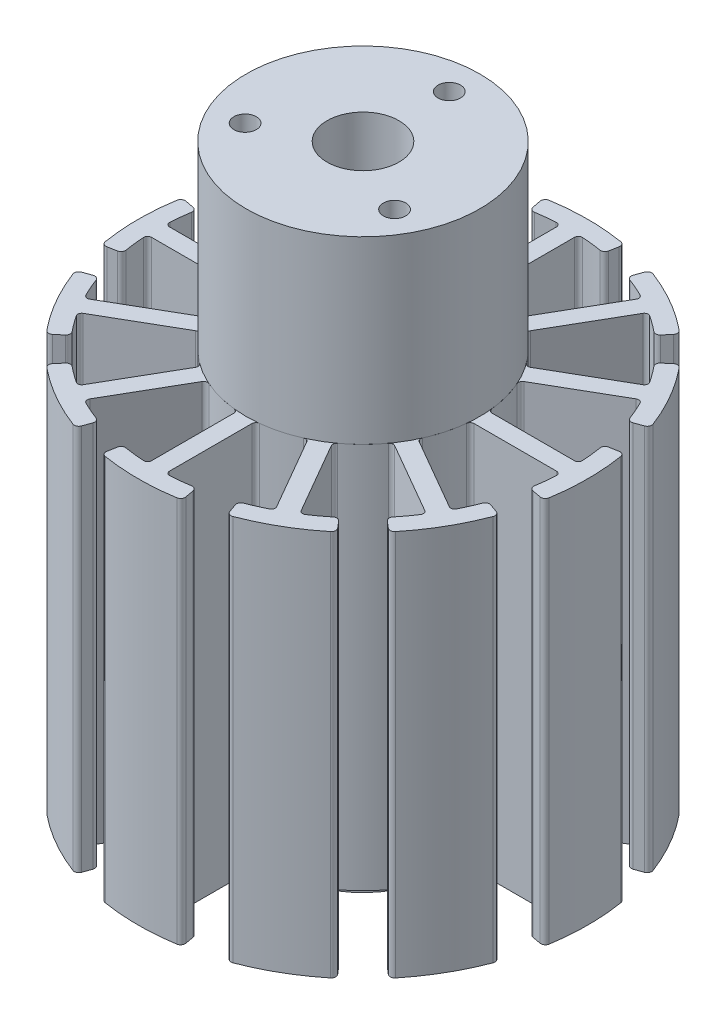
SolidWorks part; units mm, degrees
ref_plane "Front Plane" through (0, 0, 0) normal (0, 0, 1) x (1, 0, 0)
ref_plane "Top Plane" through (0, 0, 0) normal (0, 1, 0) x (1, 0, 0)
ref_plane "Right Plane" through (0, 0, 0) normal (1, 0, 0) x (0, 0, -1)
sketch "Sketch1" plane through (0, 0, 0) normal (0, 1, 0) x (1, 0, 0)
  circle A0 centre (0, 0) radius 13
  dimension "D1" = 26
extrude "Boss-Extrude1" add sketch "Sketch1" along normal blind 20
sketch "Sketch2" plane through (0, 20, 0) normal (0, 1, 0) x (1, 0, 0)
  line L0 (0, 0) -> (0, 11.9477) construction
  circle A0 centre (0, 9.6) radius 1.25
  circle A1 centre (8.3138, -4.8) radius 1.25
  circle A2 centre (-8.3138, -4.8) radius 1.25
  point P12 (0, 0)
  dimension "D1" = 9.6
  dimension "D2" = 3
extrude "Cut-Extrude1" cut sketch "Sketch2" against normal blind 5
sketch "Sketch4" plane through (0, 0, 0) normal (0, -1, 0) x (1, 0, 0)
  line L6 (0, 13) -> (0, 25) construction
  line L12 (1, 13.3636) -> (1, 22.5128)
  line L13 (-1, 13.3636) -> (-1, 22.5128)
  line L15 (4.3912, 24.0981) -> (4.2119, 23.1141)
  line L17 (-4.3912, 24.0981) -> (-4.2119, 23.1141)
  line L18 (4.1232, 22.6274) -> (4.4817, 24.595) construction
  line L19 (-4.1232, 22.6274) -> (-4.4817, 24.595) construction
  line L20 (15.8519, 18.674) -> (15.2046, 17.9114)
  line L21 (8.2462, 23.0651) -> (7.9094, 22.1233)
  line L22 (14.8845, 17.5343) -> (16.1788, 19.059) construction
  line L23 (7.7429, 21.6575) -> (8.4162, 23.5408) construction
  line L24 (7.5478, 11.0732) -> (12.1224, 18.9967)
  line L25 (5.8158, 12.0732) -> (10.3904, 19.9967)
  line L26 (23.0651, 8.2462) -> (22.1233, 7.9094)
  line L27 (18.674, 15.8519) -> (17.9114, 15.2046)
  line L28 (21.6575, 7.7429) -> (23.5408, 8.4162) construction
  line L29 (17.5343, 14.8845) -> (19.059, 16.1788) construction
  line L30 (12.0732, 5.8158) -> (19.9967, 10.3904)
  line L31 (11.0732, 7.5478) -> (18.9967, 12.1224)
  line L32 (24.0981, -4.3912) -> (23.1141, -4.2119)
  line L33 (24.0981, 4.3912) -> (23.1141, 4.2119)
  line L34 (22.6274, -4.1232) -> (24.595, -4.4817) construction
  line L35 (22.6274, 4.1232) -> (24.595, 4.4817) construction
  line L36 (13.3636, -1) -> (22.5128, -1)
  line L37 (13.3636, 1) -> (22.5128, 1)
  line L38 (18.674, -15.8519) -> (17.9114, -15.2046)
  line L39 (23.0651, -8.2462) -> (22.1233, -7.9094)
  line L40 (17.5343, -14.8845) -> (19.059, -16.1788) construction
  line L41 (21.6575, -7.7429) -> (23.5408, -8.4162) construction
  line L42 (11.0732, -7.5478) -> (18.9967, -12.1224)
  line L43 (12.0732, -5.8158) -> (19.9967, -10.3904)
  line L44 (8.2462, -23.0651) -> (7.9094, -22.1233)
  line L45 (15.8519, -18.674) -> (15.2046, -17.9114)
  line L46 (7.7429, -21.6575) -> (8.4162, -23.5408) construction
  line L47 (14.8845, -17.5343) -> (16.1788, -19.059) construction
  line L48 (5.8158, -12.0732) -> (10.3904, -19.9967)
  line L49 (7.5478, -11.0732) -> (12.1224, -18.9967)
  line L50 (-4.3912, -24.0981) -> (-4.2119, -23.1141)
  line L51 (4.3912, -24.0981) -> (4.2119, -23.1141)
  line L52 (-4.1232, -22.6274) -> (-4.4817, -24.595) construction
  line L53 (4.1232, -22.6274) -> (4.4817, -24.595) construction
  line L54 (-1, -13.3636) -> (-1, -22.5128)
  line L55 (1, -13.3636) -> (1, -22.5128)
  line L56 (-15.8519, -18.674) -> (-15.2046, -17.9114)
  line L57 (-8.2462, -23.0651) -> (-7.9094, -22.1233)
  line L58 (-14.8845, -17.5343) -> (-16.1788, -19.059) construction
  line L59 (-7.7429, -21.6575) -> (-8.4162, -23.5408) construction
  line L60 (-7.5478, -11.0732) -> (-12.1224, -18.9967)
  line L61 (-5.8158, -12.0732) -> (-10.3904, -19.9967)
  line L62 (-23.0651, -8.2462) -> (-22.1233, -7.9094)
  line L63 (-18.674, -15.8519) -> (-17.9114, -15.2046)
  line L64 (-21.6575, -7.7429) -> (-23.5408, -8.4162) construction
  line L65 (-17.5343, -14.8845) -> (-19.059, -16.1788) construction
  line L66 (-12.0732, -5.8158) -> (-19.9967, -10.3904)
  line L67 (-11.0732, -7.5478) -> (-18.9967, -12.1224)
  line L68 (-24.0981, 4.3912) -> (-23.1141, 4.2119)
  line L69 (-24.0981, -4.3912) -> (-23.1141, -4.2119)
  line L70 (-22.6274, 4.1232) -> (-24.595, 4.4817) construction
  line L71 (-22.6274, -4.1232) -> (-24.595, -4.4817) construction
  line L72 (-13.3636, 1) -> (-22.5128, 1)
  line L73 (-13.3636, -1) -> (-22.5128, -1)
  line L74 (-18.674, 15.8519) -> (-17.9114, 15.2046)
  line L75 (-23.0651, 8.2462) -> (-22.1233, 7.9094)
  line L76 (-17.5343, 14.8845) -> (-19.059, 16.1788) construction
  line L77 (-21.6575, 7.7429) -> (-23.5408, 8.4162) construction
  line L78 (-11.0732, 7.5478) -> (-18.9967, 12.1224)
  line L79 (-12.0732, 5.8158) -> (-19.9967, 10.3904)
  line L80 (-8.2462, 23.0651) -> (-7.9094, 22.1233)
  line L81 (-15.8519, 18.674) -> (-15.2046, 17.9114)
  line L82 (-7.7429, 21.6575) -> (-8.4162, 23.5408) construction
  line L83 (-14.8845, 17.5343) -> (-16.1788, 19.059) construction
  line L84 (-5.8158, 12.0732) -> (-10.3904, 19.9967)
  line L85 (-7.5478, 11.0732) -> (-12.1224, 18.9967)
  arc A0 (3.9789, 24.6813) -> (-3.9789, 24.6813) centre (0, 0) ccw
  arc A1 (3.6408, 22.71) -> (1.4693, 22.953) centre (0, 0) ccw
  arc A2 (-1.3938, 12.9251) -> (-5.2555, 11.8903) centre (0, 0) ccw
  circle A3 centre (0, 0) radius 13 construction
  arc A4 (-12.7489, 19.1433) -> (-14.8845, 17.5343) centre (0, 0) ccw
  arc A5 (-12.5, 21.6506) -> (-16.1788, 19.059) centre (0, 0) ccw
  arc A6 (-4.3912, 24.0981) -> (-3.9789, 24.6813) centre (-3.8993, 24.1877) cw
  arc A7 (-4.2119, 23.1141) -> (-3.6408, 22.71) centre (-3.72, 23.2037) ccw
  arc A8 (4.2119, 23.1141) -> (3.6408, 22.71) centre (3.72, 23.2037) cw
  arc A9 (3.9789, 24.6813) -> (4.3912, 24.0981) centre (3.8993, 24.1877) cw
  arc A10 (-1.4693, 22.953) -> (-3.6408, 22.71) centre (0, 0) ccw
  arc A11 (-1, 22.5128) -> (-1.4693, 22.953) centre (-1.4411, 22.5128) ccw
  arc A12 (1, 22.5128) -> (1.4693, 22.953) centre (1.4411, 22.5128) cw
  arc A13 (-1, 13.3636) -> (-1.3938, 12.9251) centre (-1.4411, 13.3636) cw
  arc A14 (1, 13.3636) -> (1.3938, 12.9251) centre (1.4411, 13.3636) ccw
  arc A15 (5.2555, 11.8903) -> (-5.2555, 11.8903) centre (0, 0) ccw
  arc A16 (15.7865, 19.3852) -> (8.8949, 23.3641) centre (0, 0) ccw
  arc A17 (14.5081, 17.847) -> (12.7489, 19.1433) centre (0, 0) ccw
  arc A18 (8.2462, 23.0651) -> (8.8949, 23.3641) centre (8.717, 22.8968) cw
  arc A19 (7.9094, 22.1233) -> (8.202, 21.4879) centre (8.3803, 21.955) ccw
  arc A20 (15.2046, 17.9114) -> (14.5081, 17.847) centre (14.8234, 18.235) cw
  arc A21 (15.7865, 19.3852) -> (15.8519, 18.674) centre (15.4707, 18.9975) cw
  arc A22 (10.2041, 20.6125) -> (8.202, 21.4879) centre (0, 0) ccw
  arc A23 (10.3904, 19.9967) -> (10.2041, 20.6125) centre (10.0084, 20.2172) ccw
  arc A24 (12.1224, 18.9967) -> (12.7489, 19.1433) centre (12.5044, 18.7761) cw
  arc A25 (5.8158, 12.0732) -> (5.2555, 11.8903) centre (5.4338, 12.2938) cw
  arc A26 (23.3641, 8.8949) -> (19.3852, 15.7865) centre (0, 0) ccw
  arc A27 (21.4879, 8.202) -> (20.6125, 10.2041) centre (0, 0) ccw
  arc A28 (18.674, 15.8519) -> (19.3852, 15.7865) centre (18.9975, 15.4707) cw
  arc A29 (17.9114, 15.2046) -> (17.847, 14.5081) centre (18.235, 14.8234) ccw
  arc A30 (22.1233, 7.9094) -> (21.4879, 8.202) centre (21.955, 8.3803) cw
  arc A31 (23.3641, 8.8949) -> (23.0651, 8.2462) centre (22.8968, 8.717) cw
  arc A32 (19.1433, 12.7489) -> (17.847, 14.5081) centre (0, 0) ccw
  arc A33 (18.9967, 12.1224) -> (19.1433, 12.7489) centre (18.7761, 12.5044) ccw
  arc A34 (19.9967, 10.3904) -> (20.6125, 10.2041) centre (20.2172, 10.0084) cw
  arc A35 (11.0732, 7.5478) -> (10.4965, 7.6696) centre (10.8527, 7.9298) cw
  arc A36 (24.6813, -3.9789) -> (24.6813, 3.9789) centre (0, 0) ccw
  arc A37 (22.71, -3.6408) -> (22.953, -1.4693) centre (0, 0) ccw
  arc A38 (24.0981, 4.3912) -> (24.6813, 3.9789) centre (24.1877, 3.8993) cw
  arc A39 (23.1141, 4.2119) -> (22.71, 3.6408) centre (23.2037, 3.72) ccw
  arc A40 (23.1141, -4.2119) -> (22.71, -3.6408) centre (23.2037, -3.72) cw
  arc A41 (24.6813, -3.9789) -> (24.0981, -4.3912) centre (24.1877, -3.8993) cw
  arc A42 (22.953, 1.4693) -> (22.71, 3.6408) centre (0, 0) ccw
  arc A43 (22.5128, 1) -> (22.953, 1.4693) centre (22.5128, 1.4411) ccw
  arc A44 (22.5128, -1) -> (22.953, -1.4693) centre (22.5128, -1.4411) cw
  arc A45 (13.3636, 1) -> (12.9251, 1.3938) centre (13.3636, 1.4411) cw
  arc A46 (19.3852, -15.7865) -> (23.3641, -8.8949) centre (0, 0) ccw
  arc A47 (17.847, -14.5081) -> (19.1433, -12.7489) centre (0, 0) ccw
  arc A48 (23.0651, -8.2462) -> (23.3641, -8.8949) centre (22.8968, -8.717) cw
  arc A49 (22.1233, -7.9094) -> (21.4879, -8.202) centre (21.955, -8.3803) ccw
  arc A50 (17.9114, -15.2046) -> (17.847, -14.5081) centre (18.235, -14.8234) cw
  arc A51 (19.3852, -15.7865) -> (18.674, -15.8519) centre (18.9975, -15.4707) cw
  arc A52 (20.6125, -10.2041) -> (21.4879, -8.202) centre (0, 0) ccw
  arc A53 (19.9967, -10.3904) -> (20.6125, -10.2041) centre (20.2172, -10.0084) ccw
  arc A54 (18.9967, -12.1224) -> (19.1433, -12.7489) centre (18.7761, -12.5044) cw
  arc A55 (12.0732, -5.8158) -> (11.8903, -5.2555) centre (12.2938, -5.4338) cw
  arc A56 (8.8949, -23.3641) -> (15.7865, -19.3852) centre (0, 0) ccw
  arc A57 (8.202, -21.4879) -> (10.2041, -20.6125) centre (0, 0) ccw
  arc A58 (15.8519, -18.674) -> (15.7865, -19.3852) centre (15.4707, -18.9975) cw
  arc A59 (15.2046, -17.9114) -> (14.5081, -17.847) centre (14.8234, -18.235) ccw
  arc A60 (7.9094, -22.1233) -> (8.202, -21.4879) centre (8.3803, -21.955) cw
  arc A61 (8.8949, -23.3641) -> (8.2462, -23.0651) centre (8.717, -22.8968) cw
  arc A62 (12.7489, -19.1433) -> (14.5081, -17.847) centre (0, 0) ccw
  arc A63 (12.1224, -18.9967) -> (12.7489, -19.1433) centre (12.5044, -18.7761) ccw
  arc A64 (10.3904, -19.9967) -> (10.2041, -20.6125) centre (10.0084, -20.2172) cw
  arc A65 (7.5478, -11.0732) -> (7.6696, -10.4965) centre (7.9298, -10.8527) cw
  arc A66 (-3.9789, -24.6813) -> (3.9789, -24.6813) centre (0, 0) ccw
  arc A67 (-3.6408, -22.71) -> (-1.4693, -22.953) centre (0, 0) ccw
  arc A68 (4.3912, -24.0981) -> (3.9789, -24.6813) centre (3.8993, -24.1877) cw
  arc A69 (4.2119, -23.1141) -> (3.6408, -22.71) centre (3.72, -23.2037) ccw
  arc A70 (-4.2119, -23.1141) -> (-3.6408, -22.71) centre (-3.72, -23.2037) cw
  arc A71 (-3.9789, -24.6813) -> (-4.3912, -24.0981) centre (-3.8993, -24.1877) cw
  arc A72 (1.4693, -22.953) -> (3.6408, -22.71) centre (0, 0) ccw
  arc A73 (1, -22.5128) -> (1.4693, -22.953) centre (1.4411, -22.5128) ccw
  arc A74 (-1, -22.5128) -> (-1.4693, -22.953) centre (-1.4411, -22.5128) cw
  arc A75 (1, -13.3636) -> (1.3938, -12.9251) centre (1.4411, -13.3636) cw
  arc A76 (-15.7865, -19.3852) -> (-8.8949, -23.3641) centre (0, 0) ccw
  arc A77 (-14.5081, -17.847) -> (-12.7489, -19.1433) centre (0, 0) ccw
  arc A78 (-8.2462, -23.0651) -> (-8.8949, -23.3641) centre (-8.717, -22.8968) cw
  arc A79 (-7.9094, -22.1233) -> (-8.202, -21.4879) centre (-8.3803, -21.955) ccw
  arc A80 (-15.2046, -17.9114) -> (-14.5081, -17.847) centre (-14.8234, -18.235) cw
  arc A81 (-15.7865, -19.3852) -> (-15.8519, -18.674) centre (-15.4707, -18.9975) cw
  arc A82 (-10.2041, -20.6125) -> (-8.202, -21.4879) centre (0, 0) ccw
  arc A83 (-10.3904, -19.9967) -> (-10.2041, -20.6125) centre (-10.0084, -20.2172) ccw
  arc A84 (-12.1224, -18.9967) -> (-12.7489, -19.1433) centre (-12.5044, -18.7761) cw
  arc A85 (-5.8158, -12.0732) -> (-5.2555, -11.8903) centre (-5.4338, -12.2938) cw
  arc A86 (-23.3641, -8.8949) -> (-19.3852, -15.7865) centre (0, 0) ccw
  arc A87 (-21.4879, -8.202) -> (-20.6125, -10.2041) centre (0, 0) ccw
  arc A88 (-18.674, -15.8519) -> (-19.3852, -15.7865) centre (-18.9975, -15.4707) cw
  arc A89 (-17.9114, -15.2046) -> (-17.847, -14.5081) centre (-18.235, -14.8234) ccw
  arc A90 (-22.1233, -7.9094) -> (-21.4879, -8.202) centre (-21.955, -8.3803) cw
  arc A91 (-23.3641, -8.8949) -> (-23.0651, -8.2462) centre (-22.8968, -8.717) cw
  arc A92 (-19.1433, -12.7489) -> (-17.847, -14.5081) centre (0, 0) ccw
  arc A93 (-18.9967, -12.1224) -> (-19.1433, -12.7489) centre (-18.7761, -12.5044) ccw
  arc A94 (-19.9967, -10.3904) -> (-20.6125, -10.2041) centre (-20.2172, -10.0084) cw
  arc A95 (-11.0732, -7.5478) -> (-10.4965, -7.6696) centre (-10.8527, -7.9298) cw
  arc A96 (-24.6813, 3.9789) -> (-24.6813, -3.9789) centre (0, 0) ccw
  arc A97 (-22.71, 3.6408) -> (-22.953, 1.4693) centre (0, 0) ccw
  arc A98 (-24.0981, -4.3912) -> (-24.6813, -3.9789) centre (-24.1877, -3.8993) cw
  arc A99 (-23.1141, -4.2119) -> (-22.71, -3.6408) centre (-23.2037, -3.72) ccw
  arc A100 (-23.1141, 4.2119) -> (-22.71, 3.6408) centre (-23.2037, 3.72) cw
  arc A101 (-24.6813, 3.9789) -> (-24.0981, 4.3912) centre (-24.1877, 3.8993) cw
  arc A102 (-22.953, -1.4693) -> (-22.71, -3.6408) centre (0, 0) ccw
  arc A103 (-22.5128, -1) -> (-22.953, -1.4693) centre (-22.5128, -1.4411) ccw
  arc A104 (-22.5128, 1) -> (-22.953, 1.4693) centre (-22.5128, 1.4411) cw
  arc A105 (-13.3636, -1) -> (-12.9251, -1.3938) centre (-13.3636, -1.4411) cw
  arc A106 (-19.3852, 15.7865) -> (-23.3641, 8.8949) centre (0, 0) ccw
  arc A107 (-17.847, 14.5081) -> (-19.1433, 12.7489) centre (0, 0) ccw
  arc A108 (-23.0651, 8.2462) -> (-23.3641, 8.8949) centre (-22.8968, 8.717) cw
  arc A109 (-22.1233, 7.9094) -> (-21.4879, 8.202) centre (-21.955, 8.3803) ccw
  arc A110 (-17.9114, 15.2046) -> (-17.847, 14.5081) centre (-18.235, 14.8234) cw
  arc A111 (-19.3852, 15.7865) -> (-18.674, 15.8519) centre (-18.9975, 15.4707) cw
  arc A112 (-20.6125, 10.2041) -> (-21.4879, 8.202) centre (0, 0) ccw
  arc A113 (-19.9967, 10.3904) -> (-20.6125, 10.2041) centre (-20.2172, 10.0084) ccw
  arc A114 (-18.9967, 12.1224) -> (-19.1433, 12.7489) centre (-18.7761, 12.5044) cw
  arc A115 (-12.0732, 5.8158) -> (-11.8903, 5.2555) centre (-12.2938, 5.4338) cw
  arc A116 (-8.8949, 23.3641) -> (-15.7865, 19.3852) centre (0, 0) ccw
  arc A117 (-8.202, 21.4879) -> (-10.2041, 20.6125) centre (0, 0) ccw
  arc A118 (-15.8519, 18.674) -> (-15.7865, 19.3852) centre (-15.4707, 18.9975) cw
  arc A119 (-15.2046, 17.9114) -> (-14.5081, 17.847) centre (-14.8234, 18.235) ccw
  arc A120 (-7.9094, 22.1233) -> (-8.202, 21.4879) centre (-8.3803, 21.955) cw
  arc A121 (-8.8949, 23.3641) -> (-8.2462, 23.0651) centre (-8.717, 22.8968) cw
  arc A122 (-12.7489, 19.1433) -> (-14.5081, 17.847) centre (0, 0) ccw
  arc A123 (-12.1224, 18.9967) -> (-12.7489, 19.1433) centre (-12.5044, 18.7761) ccw
  arc A124 (-10.3904, 19.9967) -> (-10.2041, 20.6125) centre (-10.0084, 20.2172) cw
  arc A125 (-7.5478, 11.0732) -> (-7.6696, 10.4965) centre (-7.9298, 10.8527) cw
  arc A126 (16.1788, 19.059) -> (12.5, 21.6506) centre (0, 0) ccw
  arc A127 (14.8845, 17.5343) -> (12.7489, 19.1433) centre (0, 0) ccw
  arc A128 (23.5408, 8.4162) -> (19.059, 16.1788) centre (0, 0) ccw
  arc A129 (5.2555, 11.8903) -> (1.3938, 12.9251) centre (0, 0) ccw
  arc A130 (24.595, -4.4817) -> (24.595, 4.4817) centre (0, 0) ccw
  arc A131 (22.6274, -4.1232) -> (22.953, -1.4693) centre (0, 0) ccw
  arc A132 (19.059, -16.1788) -> (23.5408, -8.4162) centre (0, 0) ccw
  arc A133 (17.5343, -14.8845) -> (19.1433, -12.7489) centre (0, 0) ccw
  arc A134 (8.4162, -23.5408) -> (16.1788, -19.059) centre (0, 0) ccw
  arc A135 (7.7429, -21.6575) -> (10.2041, -20.6125) centre (0, 0) ccw
  arc A136 (-4.4817, -24.595) -> (4.4817, -24.595) centre (0, 0) ccw
  arc A137 (-4.1232, -22.6274) -> (-1.4693, -22.953) centre (0, 0) ccw
  arc A138 (-16.1788, -19.059) -> (-8.4162, -23.5408) centre (0, 0) ccw
  arc A139 (-14.8845, -17.5343) -> (-12.7489, -19.1433) centre (0, 0) ccw
  arc A140 (-23.5408, -8.4162) -> (-19.059, -16.1788) centre (0, 0) ccw
  arc A141 (-21.6575, -7.7429) -> (-20.6125, -10.2041) centre (0, 0) ccw
  arc A142 (-24.595, 4.4817) -> (-24.595, -4.4817) centre (0, 0) ccw
  arc A143 (-22.6274, 4.1232) -> (-22.953, 1.4693) centre (0, 0) ccw
  arc A144 (-19.059, 16.1788) -> (-23.5408, 8.4162) centre (0, 0) ccw
  arc A145 (-17.5343, 14.8845) -> (-19.1433, 12.7489) centre (0, 0) ccw
  arc A146 (7.5478, 11.0732) -> (7.6696, 10.4965) centre (7.9298, 10.8527) ccw
  arc A147 (12.0732, 5.8158) -> (11.8903, 5.2555) centre (12.2938, 5.4338) ccw
  arc A148 (13.3636, -1) -> (12.9251, -1.3938) centre (13.3636, -1.4411) ccw
  arc A149 (11.0732, -7.5478) -> (10.4965, -7.6696) centre (10.8527, -7.9298) ccw
  arc A150 (5.8158, -12.0732) -> (5.2555, -11.8903) centre (5.4338, -12.2938) ccw
  arc A151 (-1, -13.3636) -> (-1.3938, -12.9251) centre (-1.4411, -13.3636) ccw
  arc A152 (-7.5478, -11.0732) -> (-7.6696, -10.4965) centre (-7.9298, -10.8527) ccw
  arc A153 (-12.0732, -5.8158) -> (-11.8903, -5.2555) centre (-12.2938, -5.4338) ccw
  arc A154 (-13.3636, 1) -> (-12.9251, 1.3938) centre (-13.3636, 1.4411) ccw
  arc A155 (-11.0732, 7.5478) -> (-10.4965, 7.6696) centre (-10.8527, 7.9298) ccw
  arc A156 (-5.8158, 12.0732) -> (-5.2555, 11.8903) centre (-5.4338, 12.2938) ccw
  arc A157 (-20.6125, 10.2041) -> (-21.6575, 7.7429) centre (0, 0) ccw
  arc A158 (-22.953, -1.4693) -> (-22.6274, -4.1232) centre (0, 0) ccw
  arc A159 (-19.1433, -12.7489) -> (-17.5343, -14.8845) centre (0, 0) ccw
  arc A160 (-10.2041, -20.6125) -> (-7.7429, -21.6575) centre (0, 0) ccw
  arc A161 (1.4693, -22.953) -> (4.1232, -22.6274) centre (0, 0) ccw
  arc A162 (12.7489, -19.1433) -> (14.8845, -17.5343) centre (0, 0) ccw
  arc A163 (20.6125, -10.2041) -> (21.6575, -7.7429) centre (0, 0) ccw
  arc A164 (22.953, 1.4693) -> (22.6274, 4.1232) centre (0, 0) ccw
  arc A165 (19.1433, 12.7489) -> (17.5343, 14.8845) centre (0, 0) ccw
  arc A166 (10.4965, 7.6696) -> (7.6696, 10.4965) centre (0, 0) ccw
  arc A167 (10.4965, 7.6696) -> (7.6696, 10.4965) centre (0, 0) ccw
  arc A168 (12.9251, 1.3938) -> (11.8903, 5.2555) centre (0, 0) ccw
  arc A169 (12.9251, 1.3938) -> (11.8903, 5.2555) centre (0, 0) ccw
  arc A170 (11.8903, -5.2555) -> (12.9251, -1.3938) centre (0, 0) ccw
  arc A171 (11.8903, -5.2555) -> (12.9251, -1.3938) centre (0, 0) ccw
  arc A172 (7.6696, -10.4965) -> (10.4965, -7.6696) centre (0, 0) ccw
  arc A173 (7.6696, -10.4965) -> (10.4965, -7.6696) centre (0, 0) ccw
  arc A174 (1.3938, -12.9251) -> (5.2555, -11.8903) centre (0, 0) ccw
  arc A175 (1.3938, -12.9251) -> (5.2555, -11.8903) centre (0, 0) ccw
  arc A176 (-5.2555, -11.8903) -> (-1.3938, -12.9251) centre (0, 0) ccw
  arc A177 (-5.2555, -11.8903) -> (-1.3938, -12.9251) centre (0, 0) ccw
  arc A178 (-10.4965, -7.6696) -> (-7.6696, -10.4965) centre (0, 0) ccw
  arc A179 (-10.4965, -7.6696) -> (-7.6696, -10.4965) centre (0, 0) ccw
  arc A180 (-12.9251, -1.3938) -> (-11.8903, -5.2555) centre (0, 0) ccw
  arc A181 (-12.9251, -1.3938) -> (-11.8903, -5.2555) centre (0, 0) ccw
  arc A182 (-11.8903, 5.2555) -> (-12.9251, 1.3938) centre (0, 0) ccw
  arc A183 (-11.8903, 5.2555) -> (-12.9251, 1.3938) centre (0, 0) ccw
  arc A184 (-7.6696, 10.4965) -> (-10.4965, 7.6696) centre (0, 0) ccw
  arc A185 (-7.6696, 10.4965) -> (-10.4965, 7.6696) centre (0, 0) ccw
  point P18 (0, 0)
  point P44 (-1, 22.9783)
  point P48 (-1, 12.9615)
  point P340 (0, 0)
  point P375 (0, 0)
  circle M2 centre (0, 0) radius 13
  dimension "D2" = 2
  dimension "D3" = 26
  dimension "D7" = 0.5
  dimension "D8" = 0.4411
  dimension "D9" = 0.4411
  dimension "D4" = 1
  dimension "D5" = 1
  dimension "D6" = 4.5
  dimension "D10" = 12
  dimension "D11" = 12
extrude "Boss-Extrude2" add sketch "Sketch4" along normal blind 43 separate body contours A14 L12 A12 A1 A8 L15 A9 A0 A6 L17 A7 A10 A11 L13 A13 M2 | M2 | A147 L30 A34 A27 A30 L26 A31 A26 A28 L27 A29 A32 A33 L31 A35 M2 | A148 L36 A44 A37 A40 L32 A41 A36 A38 L33 A39 A42 A43 L37 A45 M2 | A146 L24 A24 A17 A20 L20 A21 A16 A18 L21 A19 A22 A23 L25 A25 M2 | A156 L84 A124 A117 A120 L80 A121 A116 A5 A118 L81 A119 A4 A123 L85 A125 M2 | A155 L78 A114 A107 A110 L74 A111 A106 A108 L75 A109 A112 A113 L79 A115 M2 | A154 L72 A104 A97 A100 L68 A101 A96 A98 L69 A99 A102 A103 L73 A105 M2 | A153 L66 A94 A87 A90 L62 A91 A86 A88 L63 A89 A92 A93 L67 A95 M2 | A152 L60 A84 A77 A80 L56 A81 A76 A78 L57 A79 A82 A83 L61 A85 M2 | A150 L48 A64 A57 A60 L44 A61 A56 A58 L45 A59 A62 A63 L49 A65 M2 | A151 L54 A74 A67 A70 L50 A71 A66 A68 L51 A69 A72 A73 L55 A75 M2 | A149 L42 A54 A47 A50 L38 A51 A46 A48 L39 A49 A52 A53 L43 A55 M2 region at (0, 0, 20.6981) region at (0, 0, 0) region at (10.349, 0, 17.9251) region at (-10.349, 0, 17.9251) region at (17.9251, 0, 10.349) region at (-17.9251, 0, 10.349) region at (20.6981, 0, 0) region at (-20.6981, 0, 0) region at (17.9251, 0, -10.349) region at (-17.9251, 0, -10.349) region at (10.349, 0, -17.9251) region at (-10.349, 0, -17.9251) region at (0, 0, -20.6981)
sketch "Sketch5" plane through (0, 0, 0) normal (0, 0, 1) x (1, 0, 0)
  line L0 (0, 0) -> (0, -37.4719)
sketch "Sketch6" plane through (0, -43, 0) normal (0, -1, 0) x (-1, 0, 0)
  circle A0 centre (0, 0) radius 9
  dimension "D1" = 18
extrude "Boss-Extrude3" add sketch "Sketch6" along normal blind 3
sketch "Sketch7" plane through (0, -46, 0) normal (0, -1, 0) x (-1, 0, 0)
  circle A0 centre (0, 0) radius 6
  dimension "D1" = 12
extrude "Cut-Extrude2" cut sketch "Sketch7" against normal blind 3
sketch "Sketch8" plane through (0, -43, 0) normal (0, -1, 0) x (-1, 0, 0)
  circle A0 centre (0, 0) radius 4
extrude "Cut-Extrude3" cut sketch "Sketch8" against normal through all
